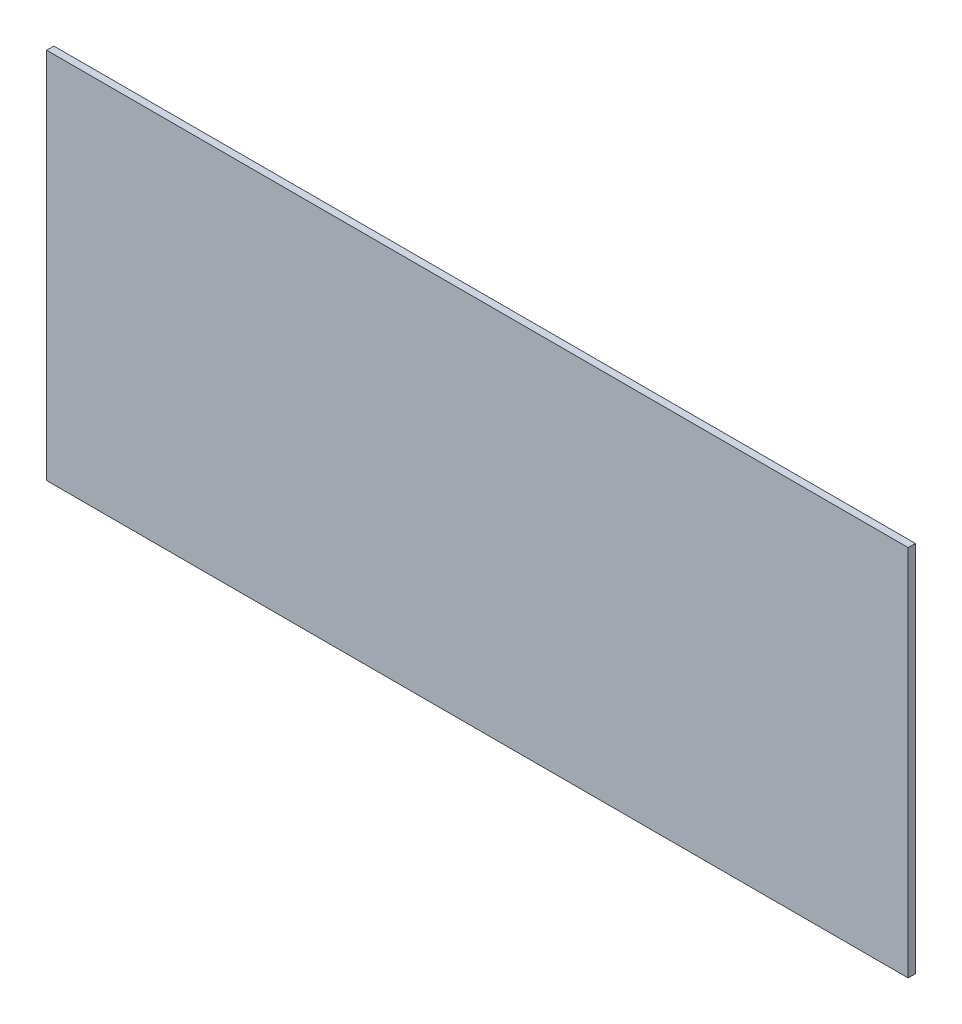
SolidWorks part; units mm, degrees
ref_plane "Front Plane" through (0, 0, 0) normal (0, 0, 1) x (1, 0, 0)
ref_plane "Top Plane" through (0, 0, 0) normal (0, 1, 0) x (1, 0, 0)
ref_plane "Right Plane" through (0, 0, 0) normal (1, 0, 0) x (0, 0, -1)
sketch "Sketch1" plane through (0, 0, 0) normal (0, 0, 1) x (1, 0, 0)
  line L1 (223.7, -24.5) -> (-169.7, -24.5)
  line L2 (223.7, -24.5) -> (223.7, 145.6824)
  line L3 (223.7, 145.6824) -> (-169.7, 145.6824)
  line L4 (-169.7, -24.5) -> (-169.7, 145.6824)
  line L5 (223.7, -24.5) -> (-169.7, 145.6824) construction
  line L6 (223.7, 145.6824) -> (-169.7, -24.5) construction
  line L7 (227, -24.5) -> (223.7, -24.5) construction
  line L9 (223.7, 145.6824) -> (54, 145.6824) construction
  line L10 (223.7, 144.1231) -> (223.7, -24.5) construction
  line L11 (-169.7, -24.5) -> (-169.7, 144.1269) construction
  point P4 (27, 60.5912)
extrude "Boss-Extrude1" add sketch "Sketch1" along normal up to surface (3.3 mm away)
